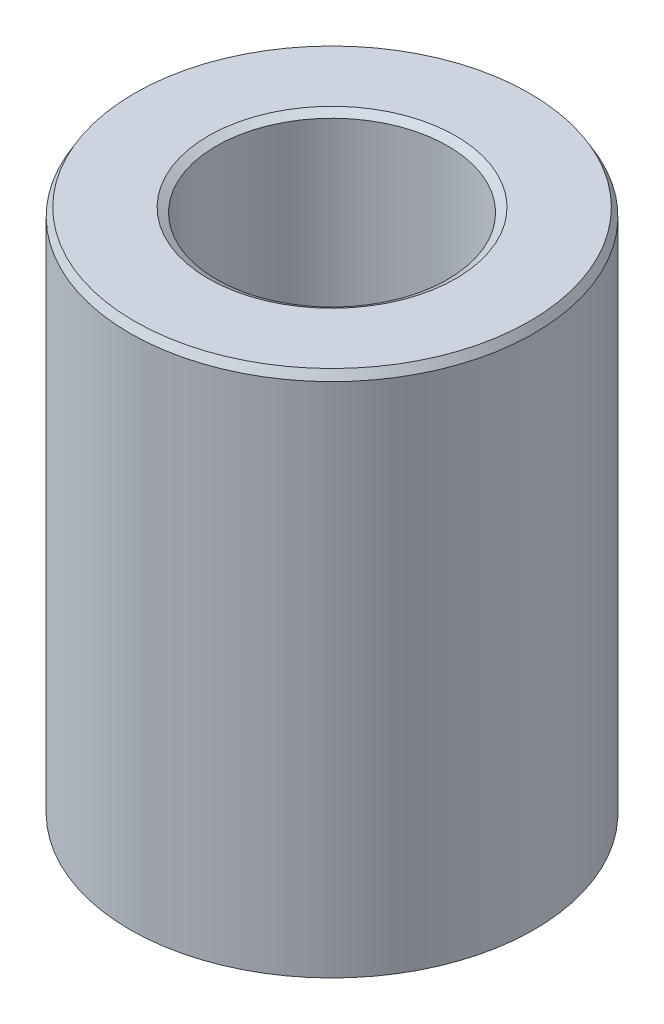
SolidWorks part; units mm, degrees
ref_plane "Front Plane" through (0, 0, 0) normal (0, 0, 1) x (1, 0, 0)
ref_plane "Top Plane" through (0, 0, 0) normal (0, 1, 0) x (1, 0, 0)
ref_plane "Right Plane" through (0, 0, 0) normal (1, 0, 0) x (0, 0, -1)
sketch "Sketch1" plane through (0, 0, 0) normal (0, 1, 0) x (1, 0, 0)
  circle A0 centre (0, 0) radius 35
  dimension "SLEEVE_OD" = 70
extrude "Boss-Extrude1" add sketch "Sketch1" along normal blind 91.6148
sketch "Sketch2" plane through (0, 0, 0) normal (0, 1, 0) x (1, 0, 0)
  circle A0 centre (0, 0) radius 20.0234
  dimension "BORE_D" = 40.0468
extrude "Cut-Extrude1" cut sketch "Sketch2" along normal through all
chamfer "Chamfer1" distance 1.3953 angle 30 4 edges at (0, 91.6148, 20.0234) (0, 0, 20.0234) (0, 0, 35) (0, 91.6148, 35) first distance on face at (0, 91.6148, 20.0234) first distance on face at (0, 0, 20.0234) first distance on face at (0, 91.6148, 35)
